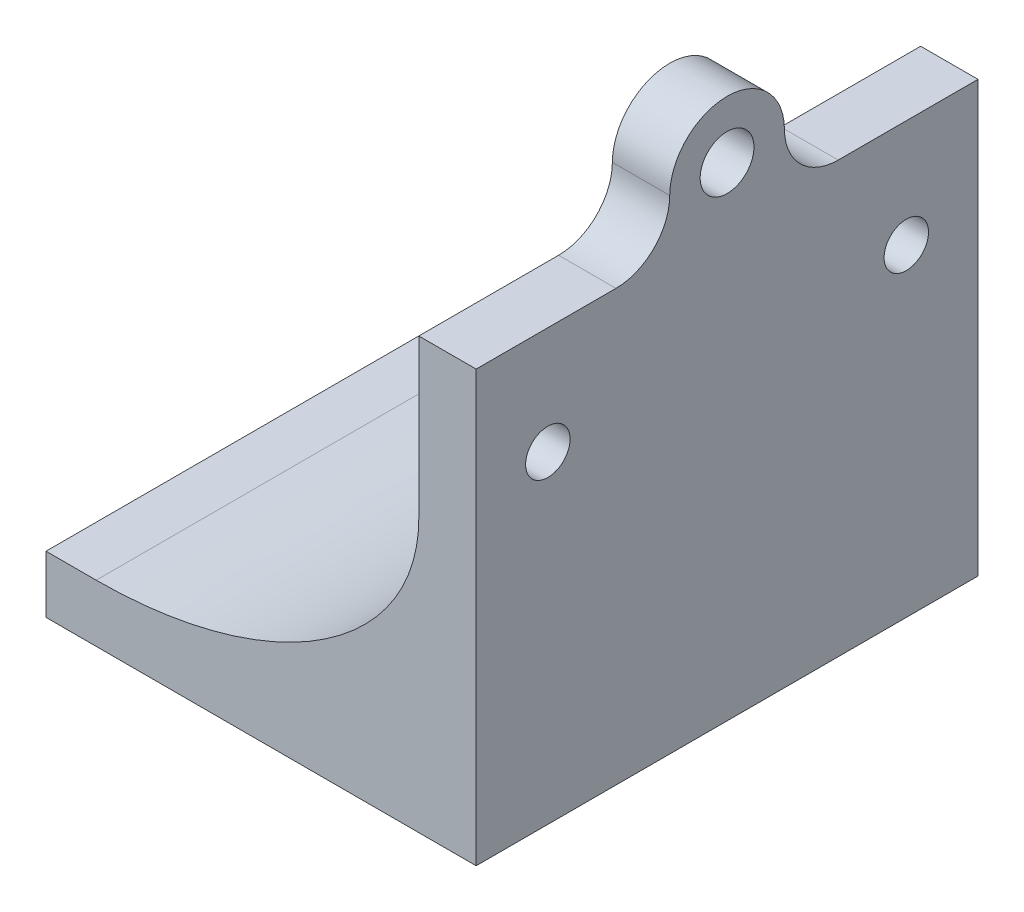
SolidWorks part; units mm, degrees
ref_plane "Plano frontal" through (0, 0, 0) normal (0, 0, 1) x (1, 0, 0)
ref_plane "Plano superior" through (0, 0, 0) normal (0, 1, 0) x (1, 0, 0)
ref_plane "Plano direito" through (0, 0, 0) normal (1, 0, 0) x (0, 0, -1)
sketch "Esboço1" plane through (0, 0, 0) normal (0, 0, 1) x (1, 0, 0)
  line L0 (0, 0) -> (0, 60)
  line L1 (0, 60) -> (-8, 60)
  line L2 (-8, 60) -> (-8, 8)
  line L3 (-8, 8) -> (-60, 8)
  line L4 (-60, 8) -> (-60, 0)
  line L5 (-60, 0) -> (0, 0)
  dimension "D1" = 60
  dimension "D2" = 8
  dimension "D3" = 8
  dimension "D4" = 60
extrude "Ressalto-extrusão1" add sketch "Esboço1" along normal blind 70
sketch "Esboço2" plane through (0, 0, 0) normal (1, 0, 0) x (0, 0, -1)
  line L0 (-60, 45) -> (-10, 45) construction
  line L1 (-70, 60) -> (0, 60) construction
  line L2 (-35, 60) -> (-35, 45) construction
  line L3 (-35, 67.4491) -> (-35, 60) construction
  circle A0 centre (-60, 45) radius 3.1
  circle A1 centre (-10, 45) radius 3.1
  circle A2 centre (-35, 67.4491) radius 30.5 construction
  dimension "D1" = 6.2
  dimension "D4" = 61
  dimension "D2" = 15
  dimension "D3" = 50
extrude "Corte-extrusão1" cut sketch "Esboço2" against normal up to next
fillet "Filete1" radius 30 1 edges at (-8, 8, 35) second distance 45 first distance on face at (-8, 48.1, 60)
sketch "Esboço3" plane through (0, 0, 0) normal (1, 0, 0) x (0, 0, -1)
  line L0 (-70, 60) -> (0, 60) construction
  line L1 (-35, 60) -> (-35, 45) construction
  line L3 (-50.4999, 60) -> (-19.5001, 60)
  arc A0 (-27, 67.4753) -> (-43, 67.4753) centre (-35, 67.4491) ccw
  circle A1 centre (-35, 67.4491) radius 3.75
  arc A2 (-50.4999, 60) -> (-43, 67.4753) centre (-50.4999, 67.5) ccw
  arc A3 (-27, 67.4753) -> (-19.5001, 60) centre (-19.5001, 67.5) ccw
  dimension "D1" = 7.5
  dimension "D2" = 8
  dimension "D3" = 15
extrude "Ressalto-extrusão2" add sketch "Esboço3" against normal up to surface (8 mm away) up to face at (-8, 48.1, 60)
